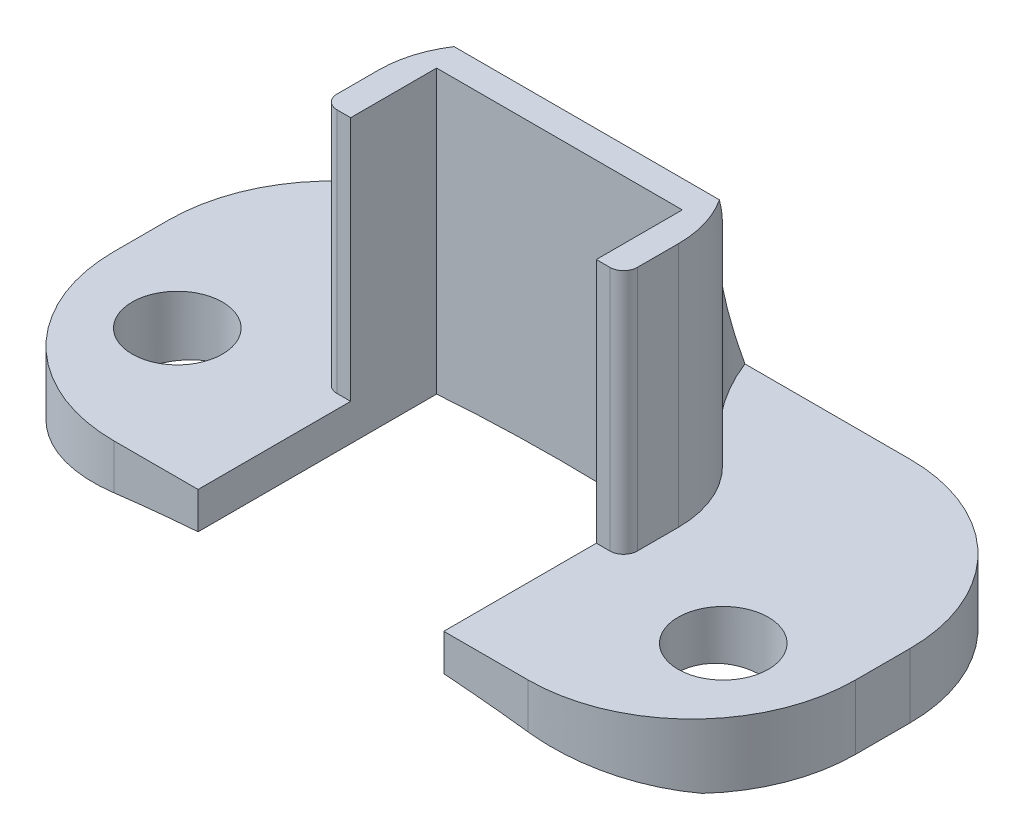
SolidWorks part; units mm, degrees
ref_plane "Front Plane" through (0, 0, 0) normal (0, 0, 1) x (1, 0, 0)
ref_plane "Top Plane" through (0, 0, 0) normal (0, 1, 0) x (1, 0, 0)
ref_plane "Right Plane" through (0, 0, 0) normal (1, 0, 0) x (0, 0, -1)
sketch "Sketch1" plane through (0, 0, 0) normal (0, 1, 0) x (1, 0, 0)
  line L0 (5.715, -10.9987) -> (6.985, -10.9987)
  line L1 (-17.2554, -0.3167) -> (17.2554, -0.3167)
  line L2 (-17.2554, -0.3167) -> (-17.2554, -18.0967)
  line L3 (-17.2554, -18.0967) -> (17.2554, -18.0967)
  line L4 (17.2554, -0.3167) -> (17.2554, -18.0967)
  line L5 (-5.715, -6.9987) -> (5.715, -6.9987)
  line L6 (-5.715, -6.9987) -> (-5.715, -15.8887)
  line L7 (-5.715, -15.8887) -> (5.715, -15.8887)
  line L8 (5.715, -6.9987) -> (5.715, -15.8887)
  line L9 (6.985, -10.9987) -> (6.985, -5.7287)
  line L10 (6.985, -5.7287) -> (-6.985, -5.7287)
  line L11 (-6.985, -5.7287) -> (-6.985, -10.9987)
  line L12 (-6.985, -10.9987) -> (-5.715, -10.9987)
  line L13 (5.715, -10.9987) -> (3.9, -10.9987)
  line L14 (3.9, -10.9987) -> (3.9, -9.9987)
  line L15 (3.9, -9.9987) -> (5.715, -9.9987)
  line L16 (-5.715, -10.9987) -> (-3.9, -10.9987)
  line L17 (-3.9, -10.9987) -> (-3.9, -9.9987)
  line L18 (-3.9, -9.9987) -> (-5.715, -9.9987)
  line L19 (-3.9, -9.9987) -> (-3.9, -6.9987)
  line L20 (3.9, -9.9987) -> (3.9, -6.9987)
  line L21 (0, -7.3881) -> (0, 0) construction
  line L22 (-5.715, -15.8887) -> (-5.715, -18.0967)
  line L23 (5.715, -15.8887) -> (5.715, -18.0967)
  line L25 (12.7, -12.0787) -> (-12.7, -12.0787) construction
  circle A0 centre (-12.7, -12.0787) radius 2.1
  circle A1 centre (12.7, -12.0787) radius 2.1
  point P23 (0, -18.0967)
  point P27 (0, -6.9987)
  point P36 (0, -12.0787)
  dimension "D10" = 4.2
  dimension "D1" = 11.43
  dimension "D2" = 8.89
  dimension "D3" = 1.27
  dimension "D4" = 1.27
  dimension "D5" = 7.8
  dimension "D6" = 3
  dimension "D7" = 1
  dimension "D8" = 17.78
  dimension "D9" = 34.5108
  dimension "D11" = 25.4
  dimension "D12" = 3.81
  dimension "D13" = 2.208
sketch "Sketch2" plane through (0, 0, 0) normal (0, 0, 1) x (1, 0, 0)
  line L0 (0, 0) -> (0, -76.859) construction
  circle A0 centre (0, -76.859) radius 78.359
  dimension "D1" = 156.718
  dimension "D2" = 76.859
ref_axis "Axis1" through (0, -76.859, 0) along (0, 0, 1)
ref_plane "Plane1" through (-5.5819, -76.4515, 0) normal (0.0728, 0.9973, 0) x (0, 0, 1)
sketch "Sketch3" plane through (-5.5819, -76.4515, 0) normal (0.0728, 0.9973, 0) x (0, 0, 1)
  line L0 (0, -72.7623) -> (0, 83.9557) construction
  circle A0 centre (0, 5.5967) radius 1.5
  dimension "D1" = 3
extrude "Boss-Extrude1" add sketch "Sketch1" along normal blind 3 contours L8 L23 L3 L4 L1 L2 L22 L6 L12 L11 L10 L9 L0 A1 A0 | L11 L12 L6 L5 L8 L0 L9 L10 | L17 L18 L6 L16 | L18 L19 L5 L6 | L20 L15 L8 L5 | L15 L14 L13 L8 region at (5.8643, 0, 10.4987) region at (4.8075, 0, 10.4987) region at (6.35, 0, 11.3869) region at (4.8075, 0, 8.4987) region at (-4.8075, 0, 10.4987) region at (-4.8075, 0, 8.4987)
extrude "Cut-Extrude1" [suppressed] cut sketch "Sketch3" along normal through all contours A0
mirror "Mirror1" [suppressed] about plane through (0, 0, 0) normal (1, 0, 0)
extrude "Boss-Extrude2" add sketch "Sketch1<8>" along normal blind 11.43 from surface contours L11 L12 L6 L5 L8 L0 L9 L10 | L15 L14 L13 L8 | L17 L18 L6 L16 region at (5.8643, 0, 10.4987) region at (4.8075, 0, 10.4987) region at (-4.8075, 0, 10.4987) starting at face at (0, 3, 10.9177)
sketch "Sketch1<8>" plane through (0, 0, 0) normal (0, 1, 0) x (1, 0, 0) same geometry as "Sketch1"
extrude "Cut-Extrude2" cut sketch "Sketch2" against normal through all both and the other way through all
sketch "Sketch4" [suppressed] plane through (0, 0, 18.0967) normal (0, 0, 1) x (1, 0, 0)
  line L1 (-17.2554, 3) -> (12.7, 3)
  line L2 (-17.2554, 3) -> (-17.2554, 0.464)
  line L3 (-17.2554, 0.464) -> (12.7, 0.464)
  line L4 (12.7, 3) -> (12.7, 0.464)
extrude "Cut-Extrude3" [suppressed] cut sketch "Sketch4" against normal up to surface (9.4726 mm away) up to face at (-5.5334, 6.2599, 10.9987)
chamfer "Chamfer1" distance 2.54 angle 45 2 edges at (5.715, 3, 8.4987) (-5.715, 3, 8.4987)
sketch "Sketch6" plane through (0, 0, 0) normal (1, 0, 0) x (0, 0, -1)
  line L0 (-5.7287, 14.43) -> (-0.3167, 3)
  line L1 (-0.3167, 3) -> (-5.7287, 3)
  line L2 (-5.7287, 3) -> (-5.7287, 14.43)
extrude "Boss-Extrude3" add sketch "Sketch6" along normal mid plane 2.54
fillet "Fillet1" radius 7.62 4 edges at (-17.2554, 1.5, 0.3167) (17.2554, 1.5, 0.3167) (17.2554, 1.5, 18.0967) (-17.2554, 1.5, 18.0967)
fillet "Fillet2" [suppressed] radius 1.27
fillet "Fillet3" [suppressed] radius 0.508
fillet "Fillet4" [suppressed] radius 1.016
fillet "Fillet5" radius 10 2 edges at (-1.27, 8.715, 5.7287) (1.27, 8.715, 5.7287)
fillet "Fillet6" radius 4.92 2 edges at (6.985, 8.715, 5.7287) (-6.985, 8.715, 5.7287)
sketch "Sketch7" plane through (0, 14.43, 0) normal (0, 1, 0) x (1, 0, 0)
  line L0 (5.715, -10.9987) -> (5.715, -18.0967) construction
  line L1 (-5.715, -6.9987) -> (5.715, -6.9987)
  line L2 (-5.715, -6.9987) -> (-5.715, -12.4326)
  line L3 (-5.715, -12.4326) -> (5.715, -12.4326)
  line L4 (5.715, -6.9987) -> (5.715, -12.4326)
extrude "Cut-Extrude4" cut sketch "Sketch7" against normal through all
fillet "Fillet7" radius 0.635 2 edges at (6.985, 8.715, 10.9987) (-6.985, 8.715, 10.9987)
equation "\"D2@Sketch2\"=(6.17/2)*1in - 1.5mm"
equation "\"D1@Sketch3\"=3mm"
